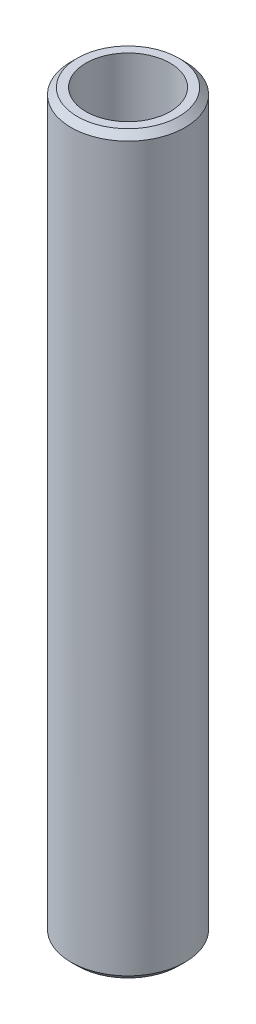
SolidWorks part; units mm, degrees
ref_plane "Front Plane" through (0, 0, 0) normal (0, 0, 1) x (1, 0, 0)
ref_plane "Top Plane" through (0, 0, 0) normal (0, 1, 0) x (1, 0, 0)
ref_plane "Right Plane" through (0, 0, 0) normal (1, 0, 0) x (0, 0, -1)
sketch "Sketch1" plane through (0, 0, 0) normal (0, 1, 0) x (1, 0, 0)
  circle A0 centre (0, 0) radius 32.5
  dimension "SHAFT_OD" = 65
extrude "Boss-Extrude1" add sketch "Sketch1" along normal blind 419.3128
sketch "Sketch2" plane through (0, 0, 0) normal (0, 1, 0) x (1, 0, 0)
  circle A0 centre (0, 0) radius 24.0054
  dimension "BORE_D" = 48.0108
extrude "Cut-Extrude1" cut sketch "Sketch2" along normal through all
chamfer "Chamfer1" distance 3.6015 angle 45 2 edges at (0, 419.3128, 32.5) (0, 0, 32.5)
